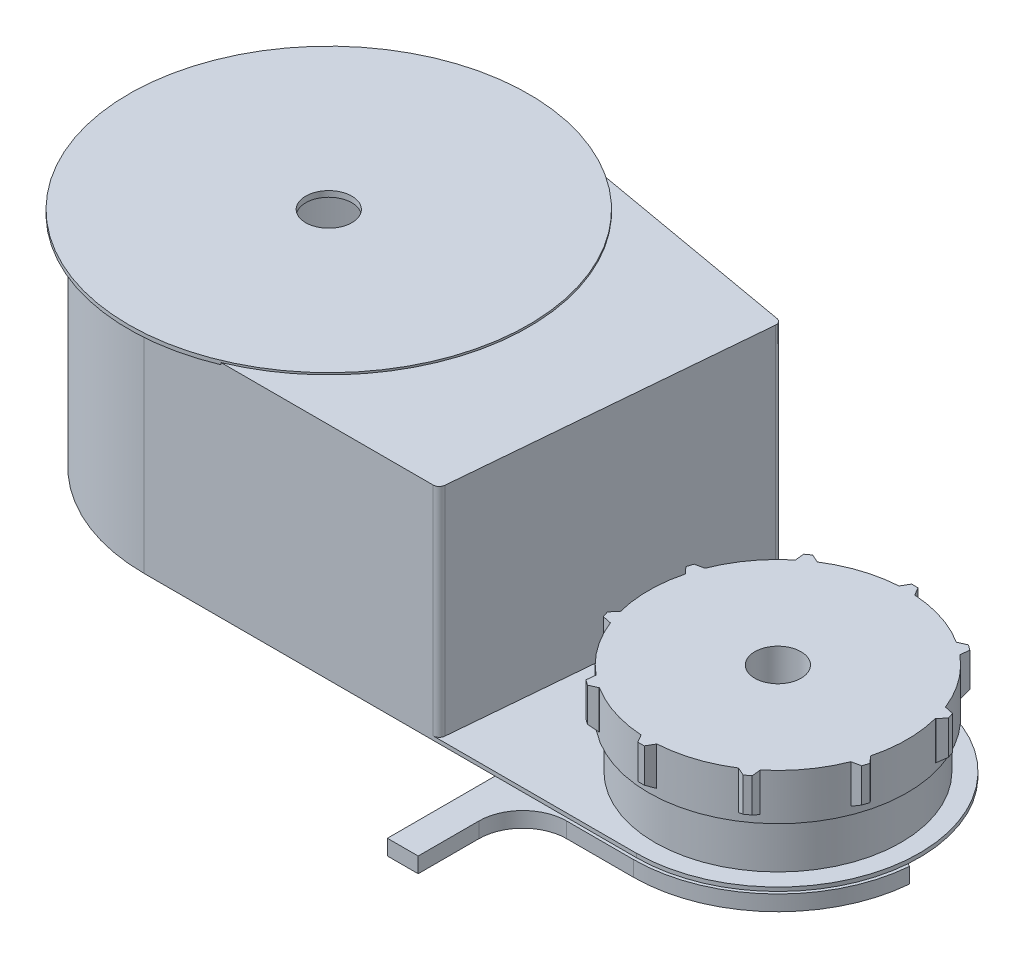
SolidWorks part; units mm, degrees
ref_plane "Front Plane" through (0, 0, 0) normal (0, 0, 1) x (1, 0, 0)
ref_plane "Top Plane" through (0, 0, 0) normal (0, 1, 0) x (1, 0, 0)
ref_plane "Right Plane" through (0, 0, 0) normal (1, 0, 0) x (0, 0, -1)
sketch "Sketch1" plane through (0, 0, 0) normal (0, 1, 0) x (1, 0, 0)
  line L0 (-203.2, -58.4223) -> (0, -58.4223)
  line L1 (-189.968, 92.82) -> (10.1449, 57.5347)
  arc A0 (-203.2, -58.4223) -> (-189.968, 92.82) centre (-203.2, 17.7777) cw
  circle A2 centre (0, 0) radius 9.525
  arc A8 (0, -58.4223) -> (10.1449, 57.5347) centre (0, 0) ccw
  dimension "D2" = 19.05
  dimension "D9" = 76.2
  dimension "D3" = 10
  dimension "D1" = 203.2
extrude "Boss-Extrude1" add sketch "Sketch1" along normal blind 1.5875
sketch "Sketch2" plane through (0, 1.5875, 0) normal (0, 1, 0) x (1, 0, 0)
  line L0 (-203.2, -58.4223) -> (0, -58.4223) construction
  line L1 (-189.968, 92.82) -> (10.1449, 57.5347) construction
  line L2 (-203.2, -58.4223) -> (-83.9298, -58.4223)
  line L3 (-189.968, 92.82) -> (-72.5098, 72.109)
  line L4 (0, 0) -> (-218.89, 19.1504) construction
  line L7 (-81.3995, -56.1037) -> (-70.4206, 69.3862)
  line L9 (-203.2, -56.8348) -> (-83.9298, -56.8348)
  line L10 (-82.981, -55.9653) -> (-72.002, 69.5246)
  line L11 (-190.2437, 91.2567) -> (-72.7855, 70.5456)
  arc A0 (-189.968, 92.82) -> (-203.2, -58.4223) centre (-203.2, 17.7777) ccw construction
  arc A1 (-189.968, 92.82) -> (-203.2, -58.4223) centre (-203.2, 17.7777) ccw
  arc A2 (-83.9298, -58.4223) -> (-81.3995, -56.1037) centre (-83.9298, -55.8823) ccw
  arc A3 (-70.4206, 69.3862) -> (-72.5098, 72.109) centre (-72.9509, 69.6076) ccw
  arc A4 (-190.2437, 91.2567) -> (-203.2, -56.8348) centre (-203.2, 17.7777) ccw
  arc A5 (-83.9298, -56.8348) -> (-82.981, -55.9653) centre (-83.9298, -55.8823) ccw
  arc A6 (-72.002, 69.5246) -> (-72.7855, 70.5456) centre (-72.9509, 69.6076) ccw
  dimension "D3" = 2.54
  dimension "D4" = 2.54
  dimension "D1" = 5
  dimension "D2" = 76.2
  dimension "D5" = 1.5875
extrude "Boss-Extrude3" add sketch "Sketch2" along normal blind 88.9
sketch "Sketch3" plane through (0, 0, 0) normal (0, -1, 0) x (1, 0, 0)
  line L0 (-58.3418, 102.8723) -> (-58.3418, -24.1083)
  line L1 (0, 0) -> (-178.2216, -15.5924) construction
  line L2 (-203.2, 58.4223) -> (0, 58.4223) construction
  line L3 (0, 0) -> (61.944, 5.4194) construction
  line L4 (-58.3418, 102.8723) -> (-45.6418, 102.8723)
  line L5 (-45.6418, 102.8723) -> (-45.6418, 77.8309)
  line L6 (0, 59.69) -> (-27.5009, 59.69)
  arc A0 (6.3428, -55.5189) -> (44.9068, -33.2559) centre (0, 0) ccw
  arc A1 (44.9068, -33.2559) -> (59.4629, 5.2023) centre (76.2, -23.1163) cw
  arc A2 (59.4629, 5.2023) -> (0, 59.69) centre (0, 0) ccw
  arc A3 (-45.6418, 77.8309) -> (-27.5009, 59.69) centre (-27.5009, 77.8309) ccw
  circle A4 centre (0, 0) radius 9.525 construction
  circle A5 centre (0, 0) radius 9.525
  spline S0 degree 3 poles (-58.3418, -24.1083) (-58.3134, -43.2841) (-57.3368, -46.3777) (-41.6621, -48.2112) (-39.6937, -54.4828) (-33.5736, -63.497) (-17.6796, -62.152) (-13.0878, -56.0963) (6.3428, -55.5189) knots 0 0 0 0 0.109377 0.144513 0.351359 0.608786 0.67365 1 1 1 1
  point P25 (-58.3418, 58.4223)
  dimension "D3" = 55.88
  dimension "D5" = 59.69
  dimension "D6" = 76.2
  dimension "D1" = 5
  dimension "D7" = 44.45
  dimension "D8" = 12.7
extrude "Boss-Extrude4" add sketch "Sketch3" along normal blind 6.35
sketch "Sketch4" plane through (0, 1.5875, 0) normal (0, 1, 0) x (1, 0, 0)
  circle A0 centre (0, 0) radius 50.8
  circle A1 centre (0, 0) radius 9.525 construction
  circle A2 centre (0, 0) radius 9.525
  dimension "D2" = 101.6
extrude "Boss-Extrude5" add sketch "Sketch4" along normal blind 19.05
sketch "Sketch5" plane through (0, 20.6375, 0) normal (0, 1, 0) x (1, 0, 0)
  circle A0 centre (0, 0) radius 53.34
  circle A1 centre (0, 0) radius 9.525 construction
  circle A2 centre (0, 0) radius 9.525
  dimension "D1" = 106.68
extrude "Boss-Extrude6" add sketch "Sketch5" along normal blind 19.05
ref_axis "Axis1" through (0, 53.0937, 0) along (0, -1, 0)
ref_plane "Plane1" through (0, 0, 53.34) normal (0, 0, 1) x (1, 0, 0)
sketch "Sketch6" plane through (0, 0, 53.34) normal (0, 0, 1) x (1, 0, 0)
  line L0 (53.34, 39.6875) -> (-53.34, 39.6875) construction
  line L1 (-3.175, 39.6875) -> (3.175, 39.6875)
  line L2 (-3.175, 39.6875) -> (-3.175, 23.8125)
  line L3 (-3.175, 23.8125) -> (3.175, 23.8125)
  line L4 (3.175, 39.6875) -> (3.175, 23.8125)
  line L5 (0, -0.8731) -> (0, 0.8731) construction
  dimension "D1" = 3.175
  dimension "D2" = 6.35
  dimension "D3" = 15.875
extrude "Boss-Extrude7" add sketch "Sketch6" along normal mid plane 6.35
chamfer "Chamfer3" distance 3.175 angle 30 3 edges at (3.175, 31.75, 56.515) (0, 23.8125, 56.515) (-3.175, 31.75, 56.515) first distance on face at (3.175, 31.75, 54.8802) first distance on face at (0, 23.8125, 54.9039) first distance on face at (-3.175, 31.75, 54.8802)
pattern_circular "CirPattern2" count 10 over 360 about axis through (0, 53.0937, 0) along (0, -1, 0) of "Chamfer3", "Boss-Extrude7"
sketch "Sketch8" plane through (0, 90.4875, 0) normal (0, 1, 0) x (1, 0, 0)
  line L0 (-203.2, -58.4223) -> (-83.9298, -58.4223) construction
  line L1 (-81.3995, -56.1037) -> (-70.4206, 69.3862) construction
  line L2 (-72.5098, 72.109) -> (-189.968, 92.82) construction
  line L3 (-203.2, -58.4223) -> (-83.9298, -58.4223)
  line L4 (-81.3995, -56.1037) -> (-70.4206, 69.3862)
  line L5 (-72.5098, 72.109) -> (-189.968, 92.82)
  arc A0 (-83.9298, -58.4223) -> (-81.3995, -56.1037) centre (-83.9298, -55.8823) ccw construction
  arc A1 (-70.4206, 69.3862) -> (-72.5098, 72.109) centre (-72.9509, 69.6076) ccw construction
  arc A2 (-189.968, 92.82) -> (-203.2, -58.4223) centre (-203.2, 17.7777) ccw construction
  arc A3 (-83.9298, -58.4223) -> (-81.3995, -56.1037) centre (-83.9298, -55.8823) ccw
  arc A4 (-70.4206, 69.3862) -> (-72.5098, 72.109) centre (-72.9509, 69.6076) ccw
  arc A5 (-189.968, 92.82) -> (-203.2, -58.4223) centre (-203.2, 17.7777) ccw
extrude "Boss-Extrude8" add sketch "Sketch8" along normal mid plane 1.5875
sketch "Sketch9" plane through (0, 91.2813, 0) normal (0, 1, 0) x (1, 0, 0)
  line L0 (0, 0) -> (-324.4671, 28.3872) construction
  line L1 (-53.6972, 0) -> (53.6972, 0) construction
  circle A2 centre (-203.2, 17.7777) radius 82.55
  dimension "D3" = 165.1
  dimension "D1" = 5
  dimension "D2" = 203.9762
extrude "Boss-Extrude9" add sketch "Sketch9" along normal mid plane 1.5875
sketch "Sketch10" plane through (0, 92.075, 0) normal (0, 1, 0) x (1, 0, 0)
  circle A0 centre (-203.2, 17.7777) radius 9.525
  circle A1 centre (-203.2, 17.7777) radius 82.55
  circle A2 centre (-203.2, 17.7777) radius 82.55 construction
  dimension "D2" = 19.05
  dimension "D1" = 0
extrude "Cut-Extrude1" cut sketch "Sketch10" against normal up to next
